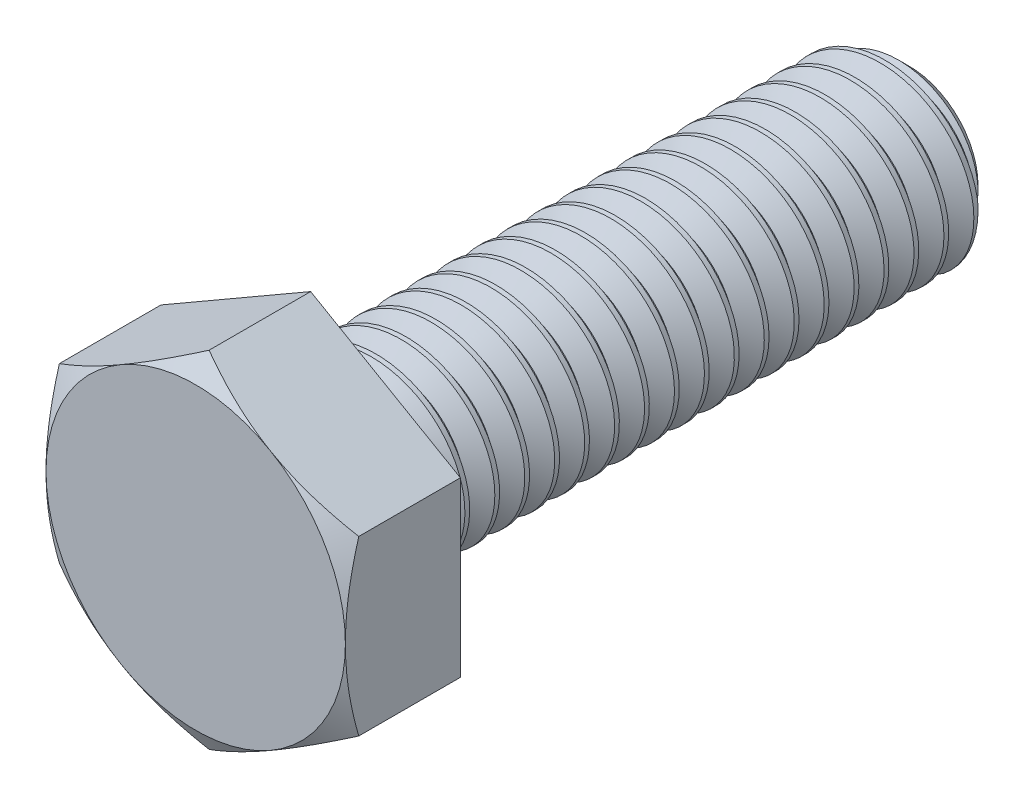
SolidWorks part; units mm, degrees
ref_plane "Front" through (0, 0, 0) normal (0, 0, 1) x (1, 0, 0)
ref_plane "Top" through (0, 0, 0) normal (0, 1, 0) x (1, 0, 0)
ref_plane "Right" through (0, 0, 0) normal (1, 0, 0) x (0, 0, -1)
sketch "Sketch1" plane through (0, 0, 0) normal (0, 0, 1) x (1, 0, 0)
  line L1 (-3.9688, -2.2914) -> (0, -4.5827)
  line L2 (0, -4.5827) -> (3.9688, -2.2914)
  line L3 (3.9688, -2.2914) -> (3.9688, 2.2914)
  line L4 (3.9688, 2.2914) -> (0, 4.5827)
  line L5 (0, 4.5827) -> (-3.9688, 2.2914)
  line L6 (-3.9688, 2.2914) -> (-3.9688, -2.2914)
  circle A0 centre (0, 0) radius 3.9688 construction
  circle A1 centre (0, 0) radius 3.9688 construction
  dimension "Head Dia" = 7.9375
extrude "Extrude3" add sketch "Sketch1" along normal blind 3.048
sketch "Sketch4" plane through (0, 0, 0) normal (1, 0, 0) x (0, 0, -1)
  line L0 (0, 0) -> (15.875, 0)
  line L3 (15.875, 0) -> (15.875, 2.413)
  line L4 (15.875, 2.413) -> (0, 2.413)
  line L6 (0, 2.413) -> (0, 0)
  line L9 (15.875, 2.413) -> (15.875, -2.413) construction
  dimension "length" = 15.875
  dimension "dia" = 4.826
revolve "Revolve1" add sketch "Sketch4" angle 360 about L0
sketch "Sketch13" plane through (0, 0, -15.875) normal (0, 0, -1) x (-1, 0, 0)
  circle A2 centre (0, 0) radius 2.413
curve "Helix/Spiral1" pitch 0.7937 height 18.923 radius 2.413 centre (0, 0, -15.875) axis (0, 0, 1) start towards (1, 0, 0)
chamfer "Chamfer2" distance 0.5953 angle 45 1 edges at (2.413, 0, -15.875)
sketch "Sketch14" plane through (0, 0, 0) normal (1, 0, 0) x (0, 0, -1)
  line L0 (15.875, 2.4378) -> (16.5695, 2.4378)
  line L1 (16.5695, 2.4378) -> (16.2719, 1.9008)
  line L2 (16.2719, 1.9008) -> (16.1727, 1.9008)
  line L3 (16.1727, 1.9008) -> (15.875, 2.4378)
  line L4 (16.0238, 2.1693) -> (16.4207, 2.1693) construction
  dimension "D1" = 0.0992
  dimension "D2" = 58
  dimension "D3" = 0.3969
  dimension "D4" = 0.0248
sweep "Cut-Sweep1" cut profiles "Sketch14" path "Helix/Spiral1" align with end faces yes
ref_plane "Plane1" through (0, 0, 22.225) normal (0, 0, -1) x (-1, 0, 0)
sketch "Sketch29" [suppressed] plane through (0, 0, 28.575) normal (0, 0, -1) x (-1, 0, 0)
  circle A0 centre (0, 0) radius 1.7526 construction
  circle A1 centre (0, 0) radius 1.7526
  point P3 (0, -1.7526)
  point P4 (0, 1.7526)
extrude "Extrude11" [suppressed] add sketch "Sketch29" against normal up to surface (28.575 mm away) up to plane "Front"
sketch "Sketch26" plane through (0, 0, 0) normal (0, 0, 1) x (1, 0, 0)
  circle A1 centre (0, 0) radius 0.5461
  dimension "D1" = 1.0922
extrude "Extrude12" add sketch "Sketch26" along normal up to surface (3.048 mm away) up to face at (0, 0, 3.048)
sketch "Sketch30" plane through (0, 0, 3.048) normal (0, 0, 1) x (1, 0, 0)
  circle A0 centre (0, 0) radius 3.9688 construction
  circle A1 centre (0, 0) radius 3.9688
extrude "Extrude13" cut sketch "Sketch30" against normal blind 2.54 draft 60 flip side to cut
sketch "Sketch18" plane through (0, 0, 0) normal (1, 0, 0) x (0, 0, -1)
  line L1 (15.875, 2.413) -> (0, 2.413) construction
  line L2 (-3.048, 3.9688) -> (-3.048, 3.437) construction
  point P0 (14.6844, -2.413)
  point P1 (15.0813, 2.413)
  point P2 (-3.048, 4.5827)
  dimension "D1" = 0.7937
  dimension "D2" = 1.1906
equation "\"D3@Helix/Spiral1\" = \"length@Sketch4\" + \"Head Ht@Extrude3\""
equation "\"D1@Sketch14\" = \"D4@Helix/Spiral1\" * .125"
equation "\"D3@Sketch14\" = \"D4@Helix/Spiral1\" * .5"
equation "\"D4@Sketch14\" = \"D1@Sketch14\" * .25"
equation "\"D1@Chamfer2\" = \"D4@Helix/Spiral1\" * .75"
equation "\"D1@Sketch18\" = \"D4@Helix/Spiral1\""
equation "\"D2@Sketch18\" = \"D4@Helix/Spiral1\" * 1.5"
